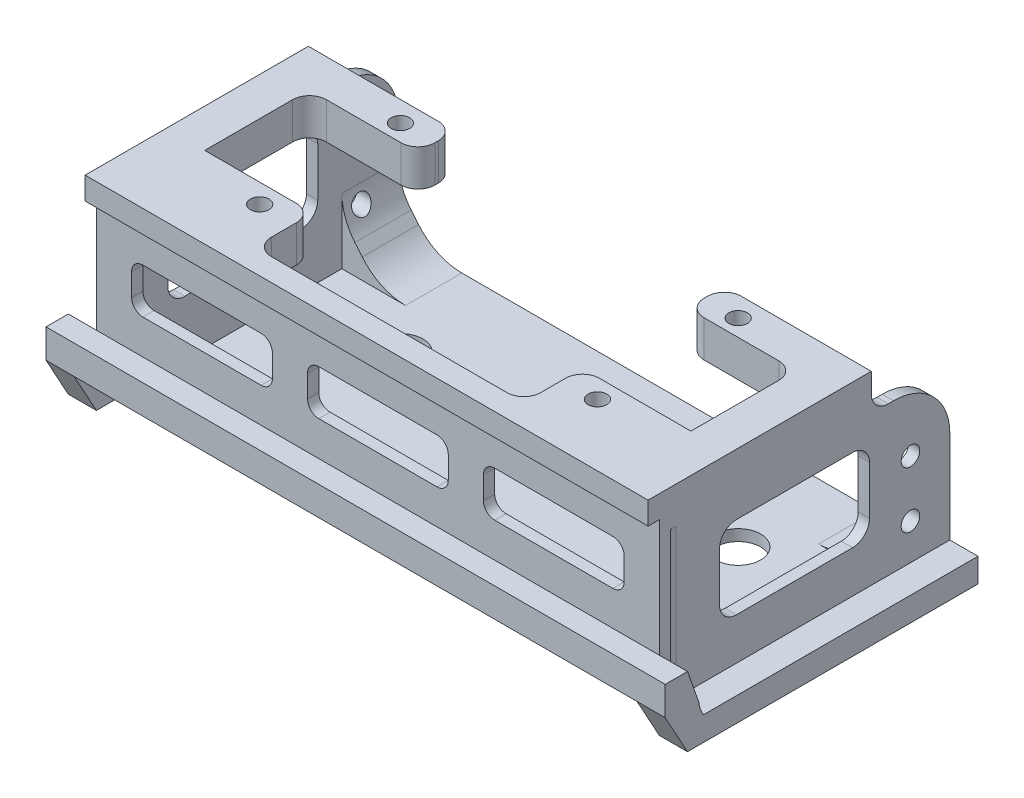
SolidWorks part; units mm, degrees
ref_plane "前视基准面" through (0, 0, 0) normal (0, 0, 1) x (1, 0, 0)
ref_plane "上视基准面" through (0, 0, 0) normal (0, 1, 0) x (1, 0, 0)
ref_plane "右视基准面" through (0, 0, 0) normal (1, 0, 0) x (0, 0, -1)
sketch "草图1" plane through (0, 0, 0) normal (0, 0, 1) x (1, 0, 0)
  line L1 (0, 0) -> (100, 0)
  line L2 (0, 0) -> (0, 30)
  line L3 (0, 30) -> (100, 30)
  line L4 (100, 0) -> (100, 30)
  dimension "D1" = 100
  dimension "D2" = 30
extrude "凸台-拉伸1" add sketch "草图1" along normal blind 2
sketch "草图2" plane through (0, 0, 2) normal (0, 0, 1) x (1, 0, 0)
  line L0 (0, 26) -> (100.6534, 26)
  line L4 (0, 30) -> (0, 0)
  line L5 (0, 0) -> (100, 0)
  line L6 (100, 0) -> (100, 30)
  line L7 (100, 30) -> (0, 30)
  line L8 (0, 30) -> (0, 0)
  line L9 (0, 0) -> (100, 0)
  line L10 (100, 0) -> (100, 30)
  line L11 (100, 30) -> (0, 30)
  line M6 (0, 30) -> (0, 0)
  line M8 (100, 0) -> (100, 30)
  line M9 (100, 30) -> (0, 30)
  dimension "D2" = 4
  dimension "D1" = 0
extrude "凸台-拉伸2" add sketch "草图2" along normal blind 2 contours L0 M6 M8 M9 region at (50, 28, 2)
sketch "草图3" plane through (0, 0, 2) normal (0, 0, 1) x (1, 0, 0)
  line L0 (37.5, 17.2904) -> (37.5, 13.2904)
  line L1 (8.25, 19.2904) -> (29.25, 19.2904)
  line L2 (6.25, 17.2904) -> (6.25, 13.2904)
  line L3 (8.25, 11.2904) -> (29.25, 11.2904)
  line L4 (100, 26) -> (0, 26)
  line L5 (0, 26) -> (0, 0)
  line L6 (0, 0) -> (100, 0)
  line L7 (100, 0) -> (100, 26)
  line L8 (100, 26) -> (0, 26)
  line L9 (0, 26) -> (0, 0)
  line L10 (0, 0) -> (100, 0)
  line L11 (100, 0) -> (100, 26)
  line L12 (31.25, 17.2904) -> (31.25, 13.2904)
  line L13 (39.5, 19.2904) -> (60.5, 19.2904)
  line L14 (62.5, 17.2904) -> (62.5, 13.2904)
  line L15 (39.5, 11.2904) -> (60.5, 11.2904)
  line L16 (68.75, 17.2904) -> (68.75, 13.2904)
  line L17 (70.75, 19.2904) -> (91.75, 19.2904)
  line L18 (93.75, 17.2904) -> (93.75, 13.2904)
  line L19 (70.75, 11.2904) -> (91.75, 11.2904)
  arc A0 (29.25, 19.2904) -> (31.25, 17.2904) centre (29.25, 17.2904) cw
  arc A1 (31.25, 13.2904) -> (29.25, 11.2904) centre (29.25, 13.2904) cw
  arc A2 (6.25, 13.2904) -> (8.25, 11.2904) centre (8.25, 13.2904) ccw
  arc A3 (6.25, 17.2904) -> (8.25, 19.2904) centre (8.25, 17.2904) cw
  arc A4 (37.5, 17.2904) -> (39.5, 19.2904) centre (39.5, 17.2904) cw
  arc A5 (37.5, 13.2904) -> (39.5, 11.2904) centre (39.5, 13.2904) ccw
  arc A6 (60.5, 19.2904) -> (62.5, 17.2904) centre (60.5, 17.2904) cw
  arc A7 (62.5, 13.2904) -> (60.5, 11.2904) centre (60.5, 13.2904) cw
  arc A8 (68.75, 17.2904) -> (70.75, 19.2904) centre (70.75, 17.2904) cw
  arc A9 (68.75, 13.2904) -> (70.75, 11.2904) centre (70.75, 13.2904) ccw
  arc A10 (91.75, 19.2904) -> (93.75, 17.2904) centre (91.75, 17.2904) cw
  arc A11 (93.75, 13.2904) -> (91.75, 11.2904) centre (91.75, 13.2904) cw
  dimension "D2" = 2
  dimension "D3" = 8
  dimension "D4" = 25
  dimension "D5" = 6.25
  dimension "D1" = 0
  dimension "D6" = 3
extrude "切除-拉伸1" cut sketch "草图3" against normal blind 2 contours L2 A2 L3 A1 L12 A0 L1 A3 | L0 A5 L15 A7 L14 A6 L13 A4 | L16 A9 L19 A11 L18 A10 L17 A8
sketch "草图4" plane through (100, 0, 0) normal (1, 0, 0) x (0, 0, -1)
  line L1 (-2, 0) -> (-5.9583, 0)
  line L2 (-2, 0) -> (-2, 5.1375)
  line L3 (-2, 5.1375) -> (-5.9583, 5.1375)
  line L4 (-5.9583, 0) -> (-5.9583, 5.1375)
  line L5 (5.0712, -5.2066) -> (49.6052, -5.2066)
  line L6 (0, 0) -> (0, 30)
  line L7 (0, 30) -> (-4, 30)
  line L8 (-4, 30) -> (-4, 26)
  line L9 (-4, 26) -> (-2, 26)
  line L10 (-2, 26) -> (-2, 0)
  line L11 (-2, 0) -> (0, 0)
  line L12 (0, 0) -> (0, 30)
  line L13 (0, 30) -> (-4, 30)
  line L14 (-4, 30) -> (-4, 26)
  line L15 (-4, 26) -> (-2, 26)
  line L16 (-2, 26) -> (-2, 0)
  line L17 (-2, 0) -> (0, 0)
  line L18 (5.0712, -5.2066) -> (5.0712, -7.2061)
  line L19 (5.0712, -7.2061) -> (49.6052, -7.2061)
  line L20 (49.6052, -5.2066) -> (49.6052, -7.2061)
  arc A0 (0, 0) -> (5.0712, -5.2066) centre (5.0693, -0.1355) ccw
  arc A1 (-2, 0) -> (5.0712, -7.2061) centre (5.0693, -0.1355) ccw
  line M11 (-2, 26) -> (-2, 0)
  line M12 (-2, 0) -> (0, 0)
  dimension "D1" = 0
extrude "凸台-拉伸3" add sketch "草图4" against normal blind 100 contours L4 L1 L3 M11 | A1 L18 A0 M12 | L20 L5 L18 L19 region at (100, 2.5687, 3.9791) region at (100, -3.9801, -1.1399) region at (100, -6.2064, -27.3382)
sketch "草图5" plane through (100, 0, 0) normal (1, 0, 0) x (0, 0, -1)
  line L0 (-2, 5.1375) -> (0, 5.1375)
  line L1 (-5.9583, 0) -> (-2.0013, -7.2061)
  line L2 (-2.0013, -7.2061) -> (17.8074, -7.2061)
  line L3 (-2, 5.1375) -> (0.8406, -2.9345)
  line L4 (0.8406, -2.9345) -> (49.6052, -2.9345)
  line L5 (49.6052, -2.9345) -> (49.6052, -7.2061)
  line L11 (0, 0) -> (0, 30)
  line L12 (0, 30) -> (-4, 30)
  line L13 (-4, 30) -> (-4, 26)
  line L14 (-4, 26) -> (-2, 26)
  line L15 (-2, 26) -> (-2, 5.1375)
  line L16 (-2, 5.1375) -> (-5.9583, 5.1375)
  line L17 (-5.9583, 5.1375) -> (-5.9583, 0)
  line L18 (-5.9583, 0) -> (-2, 0)
  line L19 (5.0712, -7.2061) -> (49.6052, -7.2061)
  line L20 (49.6052, -7.2061) -> (49.6052, -5.2066)
  line L21 (49.6052, -5.2066) -> (5.0712, -5.2066)
  line L22 (0, 0) -> (0, 30)
  line L23 (0, 30) -> (-4, 30)
  line L24 (-4, 30) -> (-4, 26)
  line L25 (-4, 26) -> (-2, 26)
  line L26 (-2, 26) -> (-2, 5.1375)
  line L27 (-2, 5.1375) -> (-5.9583, 5.1375)
  line L28 (-5.9583, 5.1375) -> (-5.9583, 0)
  line L29 (-5.9583, 0) -> (-2, 0)
  line L30 (5.0712, -7.2061) -> (49.6052, -7.2061)
  line L31 (49.6052, -7.2061) -> (49.6052, -5.2066)
  line L32 (49.6052, -5.2066) -> (5.0712, -5.2066)
  arc A2 (-2, 0) -> (5.0712, -7.2061) centre (5.0693, -0.1355) ccw
  arc A3 (0, 0) -> (5.0712, -5.2066) centre (5.0693, -0.1355) ccw
  arc A4 (-2, 0) -> (5.0712, -7.2061) centre (5.0693, -0.1355) ccw
  arc A5 (0, 0) -> (5.0712, -5.2066) centre (5.0693, -0.1355) ccw
  line M19 (-2, 5.1375) -> (-5.9583, 5.1375)
  line M20 (-5.9583, 5.1375) -> (-5.9583, 0)
  line M21 (-5.9583, 0) -> (-2, 0)
  arc M22 (-2, 0) -> (5.0712, -7.2061) centre (5.0693, -0.1355) ccw
  line M23 (5.0712, -7.2061) -> (49.6052, -7.2061)
  line M24 (49.6052, -7.2061) -> (49.6052, -5.2066)
  line M25 (49.6052, -5.2066) -> (5.0712, -5.2066)
  arc M26 (5.0712, -5.2066) -> (0, 0) centre (5.0693, -0.1355) cw
  dimension "D1" = 0
extrude "凸台-拉伸4" add sketch "草图5" along normal blind 5 contours L3 M19 M20 M21 M22 M23 M24 M25 M26 | L1 L2 M22 M21 | L5 L4 M26 M25 region at (100, -3.7867, 2.0758) region at (100, 2.079, 1.5271) region at (100, -4.0576, -25.8394)
sketch "草图6" plane through (100, 0, 0) normal (1, 0, 0) x (0, 0, -1)
  line L0 (5.0712, -5.2066) -> (49.6052, -5.2066) construction
  line L1 (5.0712, -5.2066) -> (49.6052, -5.2066)
  line L3 (0, 23.4873) -> (49.6052, 23.4873)
  line L4 (0, 23.4873) -> (0, -5.2066)
  line L5 (0, -5.2066) -> (49.6052, -5.2066)
  line L6 (-2, 26) -> (-2, 5.1375)
  line L7 (-2, 5.1375) -> (0.0197, -0.6016)
  line L8 (0, 0) -> (0, 30)
  line L9 (0, 30) -> (-4, 30)
  line L10 (-4, 30) -> (-4, 26)
  line L11 (-4, 26) -> (-2, 26)
  line L12 (-2, 26) -> (-2, 5.1375)
  line L13 (-2, 5.1375) -> (0.0197, -0.6016)
  line L14 (0, 0) -> (0, 30)
  line L15 (0, 30) -> (-4, 30)
  line L16 (-4, 30) -> (-4, 26)
  line L17 (-4, 26) -> (-2, 26)
  line L18 (49.6052, 23.4873) -> (49.6052, -5.2066)
  arc A0 (0.8406, -2.9345) -> (5.0712, -5.2066) centre (5.0693, -0.1355) ccw construction
  arc A1 (0, 0) -> (0.0197, -0.6016) centre (5.0693, -0.1355) ccw
  arc A2 (0, 0) -> (0.0197, -0.6016) centre (5.0693, -0.1355) ccw
  arc A3 (0.8406, -2.9345) -> (5.0712, -5.2066) centre (5.0693, -0.1355) ccw
  arc A4 (0.0197, -0.6016) -> (0.8406, -2.9345) centre (5.0693, -0.1355) ccw construction
  arc A5 (0.0197, -0.6016) -> (0.8406, -2.9345) centre (5.0693, -0.1355) ccw
  arc M14 (0.0197, -0.6016) -> (0, 0) centre (5.0693, -0.1355) cw
  line M15 (0, 0) -> (0, 30)
  dimension "D1" = 0
extrude "凸台-拉伸5" add sketch "草图6" against normal blind 2 contours A5 A3 L1 L18 L3 L4 M14 M15 region at (100, 9.1917, -24.8946)
fillet "圆角1" radius 3 1 edges at (100, 15.5687, 2)
sketch "草图7" plane through (0, 30, 0) normal (0, 1, 0) x (1, 0, 0)
  line L0 (50, 0) -> (50, 26.3995) construction
  line L1 (100, 1) -> (100, 49.6052) construction
  line L2 (73.9207, 0) -> (100, 0)
  line L3 (73.9207, 0) -> (73.9207, 10.4199)
  line L4 (100, 0) -> (0, 0)
  line L5 (0, 0) -> (0, -4)
  line L6 (0, -4) -> (100, -4)
  line L7 (100, -4) -> (100, 0)
  line L8 (100, 0) -> (0, 0)
  line L9 (0, 0) -> (0, -4)
  line L10 (0, -4) -> (100, -4)
  line L11 (100, -4) -> (100, 0)
  line L12 (73.9207, 10.4199) -> (100, 10.4199)
  line L13 (100, 0) -> (100, 10.4199)
  line L14 (100, 1) -> (100, 49.6052)
  line L16 (73.9207, 29.0335) -> (100, 29.0335)
  line L17 (73.9207, 29.0335) -> (73.9207, 35.6447)
  line L18 (73.9207, 35.6447) -> (100, 35.6447)
  line L19 (100, 29.0335) -> (100, 35.6447)
  line L20 (93.1845, 29.0335) -> (100, 29.0335)
  line L21 (93.1845, 29.0335) -> (93.1845, 10.4199)
  line L22 (93.1845, 10.4199) -> (100, 10.4199)
  line L23 (100, 29.0335) -> (100, 10.4199)
  circle A0 centre (80, 7) radius 1.65
  circle A1 centre (80, 32) radius 1.65
  line M14 (100, 0) -> (0, 0)
  dimension "D2" = 3.3
  dimension "D5" = 2
  dimension "D3" = 30
  dimension "D4" = 7
  dimension "D1" = 0
extrude "凸台-拉伸7" add sketch "草图7" against normal up to surface (6.5127 mm away) contours L13 L12 L3 A0 M14 | L16 L21 L12 L14 | L18 L17 L16 L14 A1 region at (87.1865, 30, -5.1518) region at (96.5922, 30, -19.7267) region at (87.3236, 30, -32.3568) up to face at (99.1742, 23.4873, -20.0406)
fillet "圆角2" radius 3 1 edges at (100, 28, 4)
fillet "圆角3" radius 3 7 edges at (73.9207, 26.7436, 0) (73.9207, 26.7436, -10.4199) (73.9207, 26.7436, -29.0335) (93.1845, 26.7436, -29.0335) (98, 11.7436, 0) (73.9207, 26.7436, -35.6447) (99, 23.4873, -35.6447)
sketch "草图8" plane through (0, 0, -49.6052) normal (0, 0, -1) x (-1, 0, 0)
  line L0 (-98, 2.7597) -> (-91.387, -5.2066)
  line L8 (0, -5.2066) -> (-98, -5.2066)
  line L9 (-98, -5.2066) -> (-98, 23.4873)
  line L10 (-98, 23.4873) -> (-100, 23.4873)
  line L11 (-100, 23.4873) -> (-100, -2.9345)
  line L12 (-100, -2.9345) -> (-105, -2.9345)
  line L13 (-105, -2.9345) -> (-105, -7.2061)
  line L14 (-105, -7.2061) -> (0, -7.2061)
  line L15 (0, -7.2061) -> (0, -5.2066)
  line L16 (0, -5.2066) -> (-98, -5.2066)
  line L17 (-98, -5.2066) -> (-98, 23.4873)
  line L18 (-98, 23.4873) -> (-100, 23.4873)
  line L19 (-100, 23.4873) -> (-100, -2.9345)
  line L20 (-100, -2.9345) -> (-105, -2.9345)
  line L21 (-105, -2.9345) -> (-105, -7.2061)
  line L22 (-105, -7.2061) -> (0, -7.2061)
  line L23 (0, -7.2061) -> (0, -5.2066)
  line M9 (0, -5.2066) -> (-98, -5.2066)
  line M10 (-98, -5.2066) -> (-98, 23.4873)
  dimension "D1" = 0
extrude "凸台-拉伸8" add sketch "草图8" against normal blind 10 contours L0 M10 M9 region at (95.7957, -2.5512, -49.6052)
fillet "圆角4" radius 10 2 edges at (91.387, -5.2066, -44.6052) (98, 2.7597, -44.6052)
fillet "圆角5" radius 10 1 edges at (99, 23.4873, -49.6052)
sketch "草图9" plane through (98, 0, 0) normal (-1, 0, 0) x (0, 0, 1)
  line L9 (-38.6447, 23.4873) -> (-39.6052, 23.4873)
  line L10 (-49.6052, 13.4873) -> (-49.6052, 6.3694)
  line L11 (-49.6052, 6.3694) -> (-39.6052, 6.3694)
  line L12 (-39.6052, 6.3694) -> (-39.6052, -5.2066)
  line L13 (-39.6052, -5.2066) -> (-5.0712, -5.2066)
  line L14 (0, -0.271) -> (0, 0)
  line L15 (-3, 4.4942) -> (-3, 23.4873)
  line L16 (-3, 23.4873) -> (-35.6447, 23.4873)
  line L17 (-35.6447, 23.4873) -> (-35.6447, 26.4873)
  line L18 (-38.6447, 23.4873) -> (-39.6052, 23.4873)
  line L19 (-49.6052, 13.4873) -> (-49.6052, 6.3694)
  line L20 (-49.6052, 6.3694) -> (-39.6052, 6.3694)
  line L21 (-39.6052, 6.3694) -> (-39.6052, -5.2066)
  line L22 (-39.6052, -5.2066) -> (-5.0712, -5.2066)
  line L23 (0, -0.271) -> (0, 0)
  line L24 (-3, 4.4942) -> (-3, 23.4873)
  line L25 (-3, 23.4873) -> (-35.6447, 23.4873)
  line L26 (-35.6447, 23.4873) -> (-35.6447, 26.4873)
  circle A0 centre (-42.6052, 13.4873) radius 1.65
  circle A1 centre (-42.6052, 3.4873) radius 1.65
  arc A4 (-39.6052, 23.4873) -> (-49.6052, 13.4873) centre (-39.6052, 13.4873) ccw
  arc A5 (-5.0712, -5.2066) -> (0, -0.271) centre (-5.0693, -0.1355) ccw
  arc A6 (0, 0) -> (-3, 4.4942) centre (-5.0693, -0.1355) ccw
  arc A7 (-38.6447, 23.4873) -> (-35.6447, 26.4873) centre (-38.6447, 26.4873) ccw
  arc A8 (-39.6052, 23.4873) -> (-49.6052, 13.4873) centre (-39.6052, 13.4873) ccw
  arc A9 (-5.0712, -5.2066) -> (0, -0.271) centre (-5.0693, -0.1355) ccw
  arc A10 (0, 0) -> (-3, 4.4942) centre (-5.0693, -0.1355) ccw
  arc A11 (-38.6447, 23.4873) -> (-35.6447, 26.4873) centre (-38.6447, 26.4873) ccw
  dimension "D3" = 3.3
  dimension "D4" = 3.3
  dimension "D2" = 10
  dimension "D5" = 10
  dimension "D6" = 7
  dimension "D1" = 0
extrude "切除-拉伸2" cut sketch "草图9" against normal blind 3.3 and the other way blind 10 contours A0 | A1 region at (98, 13.4873, -42.6052) region at (98, 3.4873, -42.6052)
ref_plane "基准面4" through (50, 0, 0) normal (1, 0, 0) x (0, 0, -1)
mirror "镜向1" about plane through (50, 0, 0) normal (1, 0, 0) of bodies 110
sketch "草图10" plane through (0, 23.4873, 0) normal (0, -1, 0) x (1, 0, 0)
  line L8 (73.9207, -3) -> (73.9207, -7.4199)
  line L9 (76.9207, -10.4199) -> (93.1845, -10.4199)
  line L10 (93.1845, -10.4199) -> (93.1845, -26.0335)
  line L11 (90.1845, -29.0335) -> (76.9207, -29.0335)
  line L12 (73.9207, -32.0335) -> (73.9207, -32.6447)
  line L13 (76.9207, -35.6447) -> (98, -35.6447)
  line L14 (98, -35.6447) -> (98, -3)
  line L15 (95, 0) -> (70.9207, 0)
  line L16 (73.9207, -3) -> (73.9207, -7.4199)
  line L17 (76.9207, -10.4199) -> (93.1845, -10.4199)
  line L18 (93.1845, -10.4199) -> (93.1845, -26.0335)
  line L19 (90.1845, -29.0335) -> (76.9207, -29.0335)
  line L20 (73.9207, -32.0335) -> (73.9207, -32.6447)
  line L21 (76.9207, -35.6447) -> (98, -35.6447)
  line L22 (98, -35.6447) -> (98, -3)
  line L23 (95, 0) -> (70.9207, 0)
  circle A0 centre (80, -32) radius 1.65 construction
  circle A1 centre (80, -32) radius 1.65
  circle A2 centre (80, -7) radius 1.65 construction
  circle A3 centre (80, -7) radius 1.65
  circle A4 centre (80, -32) radius 4
  circle A5 centre (80, -7) radius 4
  arc A6 (73.9207, -7.4199) -> (76.9207, -10.4199) centre (76.9207, -7.4199) ccw
  arc A7 (90.1845, -29.0335) -> (93.1845, -26.0335) centre (90.1845, -26.0335) ccw
  arc A8 (76.9207, -29.0335) -> (73.9207, -32.0335) centre (76.9207, -32.0335) ccw
  arc A9 (73.9207, -32.6447) -> (76.9207, -35.6447) centre (76.9207, -32.6447) ccw
  arc A10 (98, -3) -> (95, 0) centre (95, -3) ccw
  arc A11 (73.9207, -3) -> (70.9207, 0) centre (70.9207, -3) ccw
  arc A12 (73.9207, -7.4199) -> (76.9207, -10.4199) centre (76.9207, -7.4199) ccw
  arc A13 (90.1845, -29.0335) -> (93.1845, -26.0335) centre (90.1845, -26.0335) ccw
  arc A14 (76.9207, -29.0335) -> (73.9207, -32.0335) centre (76.9207, -32.0335) ccw
  arc A15 (73.9207, -32.6447) -> (76.9207, -35.6447) centre (76.9207, -32.6447) ccw
  arc A16 (98, -3) -> (95, 0) centre (95, -3) ccw
  arc A17 (73.9207, -3) -> (70.9207, 0) centre (70.9207, -3) ccw
  circle M15 centre (80, -7) radius 1.65
  circle M16 centre (80, -32) radius 1.65
  dimension "D2" = 8
  dimension "D3" = 8
  dimension "D1" = 0
extrude "切除-拉伸4" cut sketch "草图10" along normal blind 100 contours L17 A5 M15 | L17 A5 | L21 A4 L19 M16 | L19 A4 | L21 A4 | M16 | M15 region at (78.0912, 23.4873, -3.6095) region at (80, 23.4873, -10.6534) region at (80, 23.4873, -35.7874) region at (80, 23.4873, -35.5409) region at (80, 23.4873, -28.6152) region at (80, 23.4873, -32) region at (80, 23.4873, -7)
sketch "草图11" plane through (100, 0, 0) normal (1, 0, 0) x (0, 0, -1)
  line L1 (8.6896, 19.1573) -> (35.3225, 19.1573)
  line L2 (8.6896, 19.1573) -> (8.6896, 4.5186)
  line L3 (8.6896, 4.5186) -> (35.3225, 4.5186)
  line L4 (35.3225, 19.1573) -> (35.3225, 4.5186)
  line L12 (35.6447, 26.4873) -> (35.6447, 30)
  line L13 (35.6447, 30) -> (-4, 30)
  line L14 (-4, 30) -> (-4, 26)
  line L15 (-4, 26) -> (-2, 26)
  line L16 (-2, 26) -> (-2, 5.1375)
  line L17 (-2, 5.1375) -> (0.0197, -0.6016)
  line L18 (0, 0) -> (0, 23.4873)
  line L19 (0, 23.4873) -> (1, 23.4873)
  line L20 (1, 23.4873) -> (1, -2.9345)
  line L21 (1, -2.9345) -> (49.6052, -2.9345)
  line L22 (49.6052, -2.9345) -> (49.6052, 13.4873)
  line L23 (39.6052, 23.4873) -> (38.6447, 23.4873)
  line L24 (35.6447, 26.4873) -> (35.6447, 30)
  line L25 (35.6447, 30) -> (-4, 30)
  line L26 (-4, 30) -> (-4, 26)
  line L27 (-4, 26) -> (-2, 26)
  line L28 (-2, 26) -> (-2, 5.1375)
  line L29 (-2, 5.1375) -> (0.0197, -0.6016)
  line L30 (0, 0) -> (0, 23.4873)
  line L31 (0, 23.4873) -> (1, 23.4873)
  line L32 (1, 23.4873) -> (1, -2.9345)
  line L33 (1, -2.9345) -> (49.6052, -2.9345)
  line L34 (49.6052, -2.9345) -> (49.6052, 13.4873)
  line L35 (39.6052, 23.4873) -> (38.6447, 23.4873)
  arc A3 (0, 0) -> (0.0197, -0.6016) centre (5.0693, -0.1355) ccw
  arc A4 (49.6052, 13.4873) -> (39.6052, 23.4873) centre (39.6052, 13.4873) ccw
  arc A5 (35.6447, 26.4873) -> (38.6447, 23.4873) centre (38.6447, 26.4873) ccw
  arc A6 (0, 0) -> (0.0197, -0.6016) centre (5.0693, -0.1355) ccw
  arc A7 (49.6052, 13.4873) -> (39.6052, 23.4873) centre (39.6052, 13.4873) ccw
  arc A8 (35.6447, 26.4873) -> (38.6447, 23.4873) centre (38.6447, 26.4873) ccw
  dimension "D1" = 0
extrude "切除-拉伸5" cut sketch "草图11" against normal blind 120 contours L2 L1 L4 L3
mirror "镜向2" about plane through (50, 0, 0) normal (1, 0, 0) of "切除-拉伸4"
fillet "圆角6" radius 3 4 edges at (99, 19.1573, -35.3225) (99, 4.5186, -35.3225) (99, 4.5186, -8.6896) (99, 19.1573, -8.6896)
fillet "圆角7" radius 3 4 edges at (1, 19.1573, -35.3225) (1, 4.5186, -35.3225) (1, 19.1573, -8.6896) (1, 4.5186, -8.6896)
